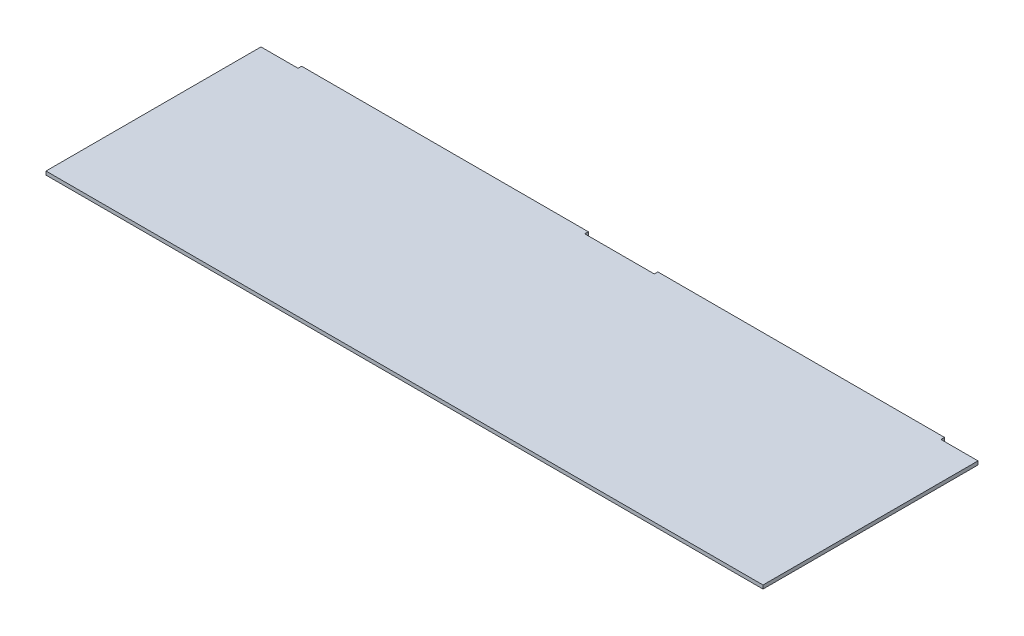
SolidWorks part; units mm, degrees
material "6061-T6 (SS)"
ref_plane "X-Y Datum" through (0, 0, 0) normal (0, 0, 1) x (1, 0, 0)
ref_plane "X-Z Datum" through (0, 0, 0) normal (0, 1, 0) x (1, 0, 0)
ref_plane "Y-Z Datum" through (0, 0, 0) normal (1, 0, 0) x (0, 0, -1)
sketch "Sketch1" plane through (0, 0, 0) normal (0, 1, 0) x (1, 0, 0)
  line L1 (-317.6778, 95.25) -> (317.6778, 95.25)
  line L2 (-317.6778, 95.25) -> (-317.6778, -95.25)
  line L3 (-317.6778, -95.25) -> (317.6778, -95.25)
  line L4 (317.6778, 95.25) -> (317.6778, -95.25)
  line L5 (-317.6778, 95.25) -> (317.6778, -95.25) construction
  line L6 (-317.6778, -95.25) -> (317.6778, 95.25) construction
  point P0 (0, 0)
  dimension "D1" = 635.3556
  dimension "D2" = 190.5
extrude "Boss-Extrude1" add sketch "Sketch1" along normal mid plane 3.175
sketch "Sketch2" plane through (0, 0, -95.25) normal (0, 0, -1) x (-1, 0, 0)
  line L20 (-317.6778, -1.5875) -> (317.6778, -1.5875) construction
  line L21 (-284.8229, -1.5875) -> (-30.8229, -1.5875)
  line L22 (30.8229, -1.5875) -> (284.8229, -1.5875)
  line L40 (30.8229, -1.5875) -> (30.8229, 1.5875)
  line L41 (30.8229, 1.5875) -> (284.8229, 1.5875)
  line L42 (284.8229, 1.5875) -> (284.8229, -1.5875)
  line L56 (-284.8229, -1.5875) -> (-284.8229, 1.5875)
  line L57 (-284.8229, 1.5875) -> (-30.8229, 1.5875)
  line L58 (-30.8229, 1.5875) -> (-30.8229, -1.5875)
extrude "Boss-Extrude2" add sketch "Sketch2" along normal blind 3.175
